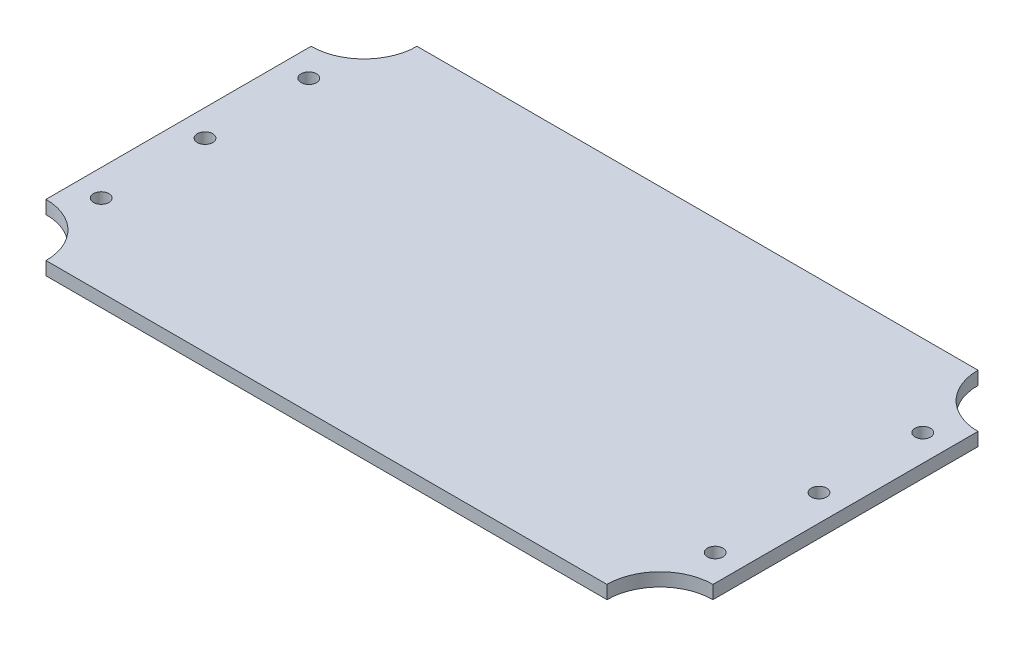
SolidWorks part; units mm, degrees
ref_plane "Спереди" through (0, 0, 0) normal (0, 0, 1) x (1, 0, 0)
ref_plane "Сверху" through (0, 0, 0) normal (0, 1, 0) x (1, 0, 0)
ref_plane "Справа" through (0, 0, 0) normal (1, 0, 0) x (0, 0, -1)
sketch "Эскиз2" plane through (0, 0, 0) normal (0, 0, 1) x (1, 0, 0)
  line L1 (-18.8586, 18.0445) -> (33.6414, 18.0445)
  line L2 (-18.8586, 18.0445) -> (-18.8586, 7.0445)
  line L3 (-9.8586, -13.9555) -> (16.6414, -13.9555)
  line L4 (34.6414, 17.0445) -> (34.6414, 7.0445)
  line L7 (33.6414, 6.0445) -> (22.6414, 6.0445)
  line L8 (17.6414, -12.9555) -> (17.6414, 1.0445)
  line L11 (-17.8586, 6.0445) -> (-10.8586, 6.0445)
  line L12 (-10.8586, -12.9555) -> (-10.8586, 6.0445)
  circle A0 centre (-0.8586, -3.9555) radius 4.5
  arc A1 (22.6414, 6.0445) -> (17.6414, 1.0445) centre (22.6414, 1.0445) ccw
  arc A2 (-17.8586, 6.0445) -> (-18.8586, 7.0445) centre (-17.8586, 7.0445) cw
  arc A3 (33.6414, 18.0445) -> (34.6414, 17.0445) centre (33.6414, 17.0445) cw
  arc A4 (33.6414, 6.0445) -> (34.6414, 7.0445) centre (33.6414, 7.0445) ccw
  arc A5 (-9.8586, -13.9555) -> (-10.8586, -12.9555) centre (-9.8586, -12.9555) cw
  arc A6 (16.6414, -13.9555) -> (17.6414, -12.9555) centre (16.6414, -12.9555) ccw
  point P12 (17.6414, 6.0445)
  point P15 (-18.8586, 6.0445)
  point P18 (34.6414, 18.0445)
  point P21 (34.6414, 6.0445)
  point P24 (-10.8586, -13.9555)
  point P27 (17.6414, -13.9555)
  dimension "D8" = 9
  dimension "D9" = 5
  dimension "D10" = 1
  dimension "D1" = 53.5
  dimension "D2" = 22
  dimension "D3" = 20
  dimension "D4" = 17
  dimension "D5" = 8
  dimension "D6" = 20
  dimension "D7" = 18
extrude "Бобышка-Вытянуть1" add sketch "Эскиз2" along normal blind 8
sketch "Эскиз3" plane through (0, 0, 8) normal (0, 0, 1) x (1, 0, 0)
  line L0 (-18.8586, 18.0445) -> (-18.8586, 7.0445) construction
  line L2 (33.6414, 18.0445) -> (-18.8586, 18.0445) construction
  line L3 (27.1414, 14.5445) -> (27.1414, 18.0445)
  line L4 (33.1414, 14.5445) -> (33.1414, 18.0445)
  line L5 (33.1414, 18.0445) -> (27.1414, 18.0445)
  line L6 (-0.3586, 14.5445) -> (-0.3586, 18.0445)
  line L7 (-6.3586, 14.5445) -> (-6.3586, 18.0445)
  line L8 (-6.3586, 18.0445) -> (-0.3586, 18.0445)
  line L9 (-6.3586, -10.4555) -> (-6.3586, -13.9555)
  line L10 (-9.8586, -13.9555) -> (16.6414, -13.9555) construction
  line L11 (-0.3586, -10.4555) -> (-0.3586, -13.9555)
  line L12 (-0.3586, -13.9555) -> (-6.3586, -13.9555)
  circle A0 centre (-3.3586, 14.5445) radius 1.5 construction
  circle A1 centre (30.1414, 14.5445) radius 1.5 construction
  circle A2 centre (-3.3586, -10.4555) radius 1.5 construction
  arc A3 (27.1414, 14.5445) -> (33.1414, 14.5445) centre (30.1414, 14.5445) ccw
  arc A4 (-6.3586, 14.5445) -> (-0.3586, 14.5445) centre (-3.3586, 14.5445) ccw
  arc A5 (-0.3586, -10.4555) -> (-0.9834, -8.6229) centre (-3.3586, -10.4555) ccw
  arc A6 (-3.5098, -7.5915) -> (-1.3272, -8.431) centre (-0.8586, -3.9555) ccw
  arc A7 (-3.8935, -7.5036) -> (-6.3586, -10.4555) centre (-3.3586, -10.4555) ccw
  arc A8 (-0.9834, -8.6229) -> (-1.3272, -8.431) centre (-1.3792, -8.9283) ccw
  arc A9 (-3.5098, -7.5915) -> (-3.8935, -7.5036) centre (-3.8044, -7.9955) ccw
  point P32 (-3.6672, -7.4714)
  dimension "D3" = 3
  dimension "D4" = 33.5
  dimension "D6" = 6
  dimension "D7" = 9
  dimension "D8" = 0.5
  dimension "D1" = 15.5
  dimension "D2" = 3.5
  dimension "D5" = 25
extrude "Бобышка-Вытянуть2" add sketch "Эскиз3" along normal blind 4 and the other way blind 11.5
sketch "Эскиз5" plane through (0, 0, 8) normal (0, 0, 1) x (1, 0, 0)
  line L1 (8.5209, 6.5605) -> (2.5209, 6.5605)
  line L2 (11.5209, 3.5605) -> (11.5209, -5.4395)
  line L3 (8.5209, -8.4395) -> (-0.4791, -8.4395)
  line L4 (-0.4791, 3.5605) -> (-0.4791, -8.4395)
  arc A0 (-1.3272, -8.431) -> (-3.5098, -7.5915) centre (-0.8586, -3.9555) ccw construction
  arc A1 (8.5209, -8.4395) -> (11.5209, -5.4395) centre (8.5209, -5.4395) ccw
  arc A2 (11.5209, 3.5605) -> (8.5209, 6.5605) centre (8.5209, 3.5605) ccw
  arc A3 (-0.4791, 3.5605) -> (2.5209, 6.5605) centre (2.5209, 3.5605) cw
  point P9 (11.5209, -8.4395)
  point P12 (11.5209, 6.5605)
  dimension "D3" = 3
  dimension "D1" = 15
  dimension "D2" = 12
extrude "Вырез-Вытянуть1" cut sketch "Эскиз5" against normal through all both and the other way through all
sketch "Эскиз6" plane through (0, 0, 8) normal (0, 0, 1) x (1, 0, 0)
  circle A0 centre (-3.3586, 14.5445) radius 1
  circle A1 centre (30.1414, 14.5445) radius 1
  circle A2 centre (-3.3586, -10.4555) radius 1
  dimension "D1" = 2
extrude "Вырез-Вытянуть2" cut sketch "Эскиз6" against normal through all both and the other way through all
sketch "Эскиз7" plane through (0, 18.0445, 0) normal (0, 1, 0) x (1, 0, 0)
  line L0 (-18.8586, -8) -> (-18.8586, 0) construction
  line L1 (-21.8586, 15.5) -> (105.1414, 15.5)
  line L2 (-33.8586, 3.5) -> (-33.8586, -56.5)
  line L3 (-21.8586, -68.5) -> (105.1414, -68.5)
  line L4 (117.1414, 3.5) -> (117.1414, -56.5)
  line L5 (-33.8586, -26.5) -> (117.1414, -26.5) construction
  line L6 (-0.3586, 3.5) -> (-6.3586, 3.5) construction
  line L7 (41.6414, 15.5) -> (41.6414, -68.5) construction
  arc A0 (-33.8586, 3.5) -> (-21.8586, 15.5) centre (-33.8586, 15.5) ccw
  arc A1 (105.1414, 15.5) -> (117.1414, 3.5) centre (117.1414, 15.5) ccw
  arc A2 (117.1414, -56.5) -> (105.1414, -68.5) centre (117.1414, -68.5) ccw
  arc A3 (-21.8586, -68.5) -> (-33.8586, -56.5) centre (-33.8586, -68.5) ccw
  circle A4 centre (-27.8586, -26.5) radius 1.75
  circle A5 centre (-27.8586, -50) radius 1.75
  circle A6 centre (-27.8586, -3) radius 1.75
  circle A7 centre (111.1414, -50) radius 1.75
  circle A8 centre (111.1414, -26.5) radius 1.75
  circle A9 centre (111.1414, -3) radius 1.75
  point P14 (41.6414, -26.5)
  dimension "D3" = 24
  dimension "D7" = 3.5
  dimension "D2" = 84
  dimension "D4" = 12
  dimension "D8" = 23.5
  dimension "D6" = 23.5
  dimension "D9" = 6
  dimension "D5" = 60.5
  dimension "D1" = 151
extrude "Бобышка-Вытянуть3" add sketch "Эскиз7" along normal blind 3
sketch "Эскиз8" plane through (0, 18.0445, 0) normal (0, -1, 0) x (1, 0, 0)
  line L0 (117.1414, 56.5) -> (117.1414, -3.5) construction
  line L1 (100.1414, 31) -> (54.1414, 31)
  line L2 (102.1414, 29) -> (102.1414, 28)
  line L3 (100.1414, 26) -> (54.1414, 26)
  line L4 (52.1414, 29) -> (52.1414, 28)
  line L5 (33.1414, 12) -> (27.1414, 12) construction
  line L6 (52.1414, 28.5) -> (102.1414, 28.5) construction
  arc A0 (102.1414, 28) -> (100.1414, 26) centre (100.1414, 28) cw
  arc A1 (102.1414, 29) -> (100.1414, 31) centre (100.1414, 29) ccw
  arc A2 (54.1414, 26) -> (52.1414, 28) centre (54.1414, 28) cw
  arc A3 (52.1414, 29) -> (54.1414, 31) centre (54.1414, 29) cw
  point P10 (102.1414, 26)
  point P13 (102.1414, 31)
  point P16 (52.1414, 26)
  dimension "D5" = 2
  dimension "D1" = 5
  dimension "D2" = 50
  dimension "D3" = 15
  dimension "D4" = 14
extrude "Бобышка-Вытянуть4" add sketch "Эскиз8" along normal blind 5
sketch "Эскиз9" plane through (0, 13.0445, 0) normal (0, -1, 0) x (1, 0, 0)
  line L0 (52.1414, 28.5) -> (102.1414, 28.5) construction
  line L1 (52.1414, 29) -> (52.1414, 28) construction
  line L2 (102.1414, 28) -> (102.1414, 29) construction
  line L3 (77.1414, 31) -> (77.1414, 26) construction
  line L4 (100.1414, 31) -> (54.1414, 31) construction
  line L5 (54.1414, 26) -> (100.1414, 26) construction
  circle A0 centre (77.1414, 28.5) radius 1
  circle A1 centre (82.1414, 28.5) radius 1
  circle A2 centre (87.1414, 28.5) radius 1
  circle A3 centre (92.1414, 28.5) radius 1
  circle A4 centre (97.1414, 28.5) radius 1
  circle A5 centre (57.1414, 28.5) radius 1
  circle A6 centre (62.1414, 28.5) radius 1
  circle A7 centre (67.1414, 28.5) radius 1
  circle A8 centre (72.1414, 28.5) radius 1
  dimension "D1" = 2
  dimension "D2" = 5
extrude "Вырез-Вытянуть3" cut sketch "Эскиз9" against normal blind 5
sketch "Эскиз10" plane through (0, 18.0445, 0) normal (0, -1, 0) x (1, 0, 0)
  line L0 (-33.8586, -3.5) -> (-33.8586, 56.5) construction
  line L1 (36.1414, 57.5) -> (80.1414, 57.5) construction
  line L2 (36.1414, 57.5) -> (36.1414, 36.5) construction
  line L3 (36.1414, 36.5) -> (80.1414, 36.5) construction
  line L4 (80.1414, 57.5) -> (80.1414, 36.5) construction
  line L5 (105.1414, -15.5) -> (-21.8586, -15.5) construction
  line L6 (3.1414, 57.5) -> (3.1414, 29.5) construction
  line L7 (-21.8586, 57.5) -> (28.1414, 57.5) construction
  line L8 (-21.8586, 57.5) -> (-21.8586, 29.5) construction
  line L9 (-21.8586, 29.5) -> (28.1414, 29.5) construction
  line L10 (28.1414, 57.5) -> (28.1414, 29.5) construction
  line L11 (-21.8586, 43.5) -> (28.1414, 43.5) construction
  circle A0 centre (42.6414, 55) radius 3.5
  circle A1 centre (73.6414, 39) radius 3.5
  circle A2 centre (42.6414, 55) radius 1
  circle A3 centre (73.6414, 39) radius 1
  circle A4 centre (-18.2586, 54) radius 3.5
  circle A5 centre (-18.2586, 54) radius 1
  circle A6 centre (24.5414, 54) radius 1
  circle A7 centre (24.5414, 54) radius 3.5
  circle A8 centre (24.5414, 33) radius 1
  circle A9 centre (24.5414, 33) radius 3.5
  circle A10 centre (-18.2586, 33) radius 1
  circle A11 centre (-18.2586, 33) radius 3.5
  point P20 (3.1414, 57.5)
  point P21 (-21.8586, 43.5)
  dimension "D3" = 7
  dimension "D6" = 6.5
  dimension "D10" = 2
  dimension "D1" = 44
  dimension "D2" = 21
  dimension "D4" = 6.5
  dimension "D5" = 2.5
  dimension "D7" = 2.5
  dimension "D8" = 70
  dimension "D9" = 52
  dimension "D11" = 50
  dimension "D12" = 28
  dimension "D13" = 12
  dimension "D14" = 45
  dimension "D15" = 21.4
  dimension "D16" = 10.5
extrude "Бобышка-Вытянуть5" add sketch "Эскиз10" along normal blind 4
equation "\"D6@Эскиз7\"=\"D8@Эскиз7\""
